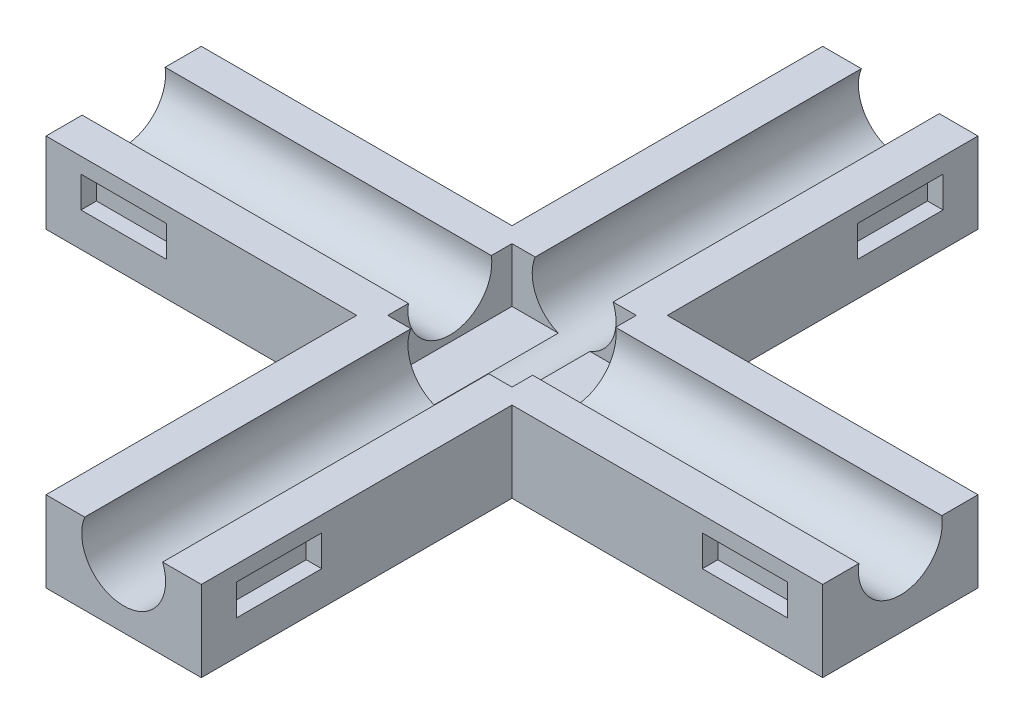
SolidWorks part; units mm, degrees
ref_plane "Front Plane" through (0, 0, 0) normal (0, 0, 1) x (1, 0, 0)
ref_plane "Top Plane" through (0, 0, 0) normal (0, 1, 0) x (1, 0, 0)
ref_plane "Right Plane" through (0, 0, 0) normal (1, 0, 0) x (0, 0, -1)
ref_plane "Plane1" through (0, 1, 0) normal (0, 1, 0) x (1, 0, 0)
ref_axis "Axis1" through (0, 4.725, 0) along (0, -1, 0)
sketch "Sketch3" plane through (0, 0, 0) normal (0, 1, 0) x (1, 0, 0)
  line L1 (5, 5) -> (25, 5)
  line L2 (-5, 25) -> (5, 25)
  line L3 (-5, 25) -> (-5, 5)
  line L5 (5, 25) -> (5, 5)
  line L7 (5, -5) -> (25, -5)
  line L8 (25, 5) -> (25, -5)
  line L10 (5, -5) -> (5, -25)
  line L11 (5, -25) -> (-5, -25)
  line L12 (-5, -5) -> (-5, -25)
  line L13 (-5, -5) -> (-25, -5)
  line L15 (-5, 5) -> (-25, 5)
  line L16 (-25, -5) -> (-25, 5)
  point P11 (0, 25)
  point P15 (-25, 0)
  dimension "D1" = 10
  dimension "D3" = 20
extrude "Boss-Extrude5" add sketch "Sketch3" along normal blind 5.2
sketch "Sketch4" plane through (0, 0, 25) normal (0, 0, 1) x (1, 0, 0)
  line L1 (-5, 0) -> (5, 0) construction
  line L2 (-5, 5.2) -> (5, 5.2) construction
  circle A0 centre (0, 4.2) radius 2.7
  point P5 (0, 0)
  dimension "D1" = 5.4
  dimension "D2" = 1
extrude "Cut-Extrude1" cut sketch "Sketch4" against normal up to next
sketch "Sketch5" plane through (25, 0, 0) normal (1, 0, 0) x (0, 0, -1)
  line L0 (-5, 0) -> (5, 0) construction
  line L1 (-5, 5.2) -> (5, 5.2) construction
  circle A0 centre (0, 4.8) radius 2.7
  point P4 (0, 0)
  dimension "D1" = 5.4
  dimension "D2" = 0.4
extrude "Cut-Extrude2" cut sketch "Sketch5" against normal through all
sketch "Sketch6" plane through (0, 5.2, 0) normal (0, 1, 0) x (1, 0, 0)
  line L1 (4, 4) -> (-4, 4)
  line L2 (4, 4) -> (4, -4)
  line L3 (4, -4) -> (-4, -4)
  line L4 (-4, 4) -> (-4, -4)
  line L5 (4, 4) -> (-4, -4) construction
  line L6 (4, -4) -> (-4, 4) construction
  point P0 (0, 0)
  dimension "D1" = 8
  dimension "D2" = 8
extrude "Cut-Extrude3" cut sketch "Sketch6" against normal blind 3.5
sketch "Sketch7" plane through (0, 0, 5) normal (0, 0, 1) x (1, 0, 0)
  line L0 (25, 5.2) -> (25, 0) construction
  line L1 (17.25, 2.2) -> (22.75, 2.2)
  line L2 (17.25, 2.2) -> (17.25, 4.2)
  line L3 (17.25, 4.2) -> (22.75, 4.2)
  line L4 (22.75, 2.2) -> (22.75, 4.2)
  line L5 (17.25, 2.2) -> (22.75, 4.2) construction
  line L6 (17.25, 4.2) -> (22.75, 2.2) construction
  line L7 (5, 5.2) -> (25, 5.2) construction
  point P0 (20, 3.2)
  dimension "D1" = 5
  dimension "D2" = 5.5
  dimension "D3" = 2
  dimension "D4" = 1
extrude "Cut-Extrude4" cut sketch "Sketch7" against normal blind 1
mirror "Mirror1" about plane through (0, 0, 0) normal (0, 0, 1) of "Cut-Extrude4"
pattern_circular "CirPattern1" count 4 over 360 about axis through (0, 4.725, 0) along (0, -1, 0) of "Mirror1"
sketch "Sketch8" plane through (0, 0, 0) normal (0, 1, 0) x (1, 0, 0)
  line L1 (-5, 5) -> (5, 5)
  line L2 (-5, 5) -> (-5, -5)
  line L3 (-5, -5) -> (5, -5)
  line L4 (5, 5) -> (5, -5)
  line L5 (-5, 5) -> (5, -5) construction
  line L6 (-5, -5) -> (5, 5) construction
  point P0 (0, 0)
extrude "Boss-Extrude6" [suppressed] add sketch "Sketch8" along normal blind 10 separate body
other "Intersect1" [suppressed]
